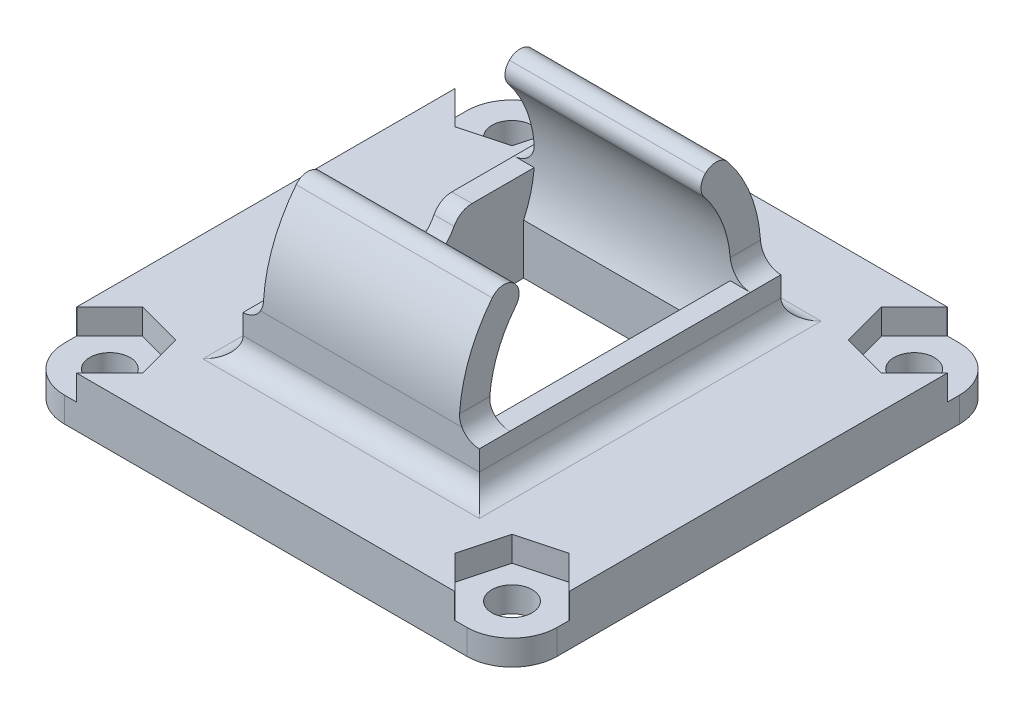
SolidWorks part; units mm, degrees
ref_plane "Front Plane" through (0, 0, 0) normal (0, 0, 1) x (1, 0, 0)
ref_plane "Top Plane" through (0, 0, 0) normal (0, 1, 0) x (1, 0, 0)
ref_plane "Right Plane" through (0, 0, 0) normal (1, 0, 0) x (0, 0, -1)
sketch "Sketch1" plane through (0, 0, 0) normal (0, 1, 0) x (1, 0, 0)
  line L1 (10, 10) -> (-10, 10)
  line L2 (10, 10) -> (10, -10)
  line L3 (10, -10) -> (-10, -10)
  line L4 (-10, 10) -> (-10, -10)
  line L5 (10, 10) -> (-10, -10) construction
  line L6 (10, -10) -> (-10, 10) construction
  circle A0 centre (-10, 10) radius 1
  circle A1 centre (10, 10) radius 1
  circle A2 centre (10, -10) radius 2.25
  circle A3 centre (-10, -10) radius 1
  circle A4 centre (-10, 10) radius 2.25
  circle A5 centre (10, 10) radius 2.25
  circle A6 centre (10, -10) radius 1
  circle A7 centre (-10, -10) radius 2.25
  point P0 (0, 0)
  dimension "D2" = 2
  dimension "D3" = 4.5
  dimension "D1" = 20
extrude "Boss-Extrude1" add sketch "Sketch1" along normal blind 2.5 contours A7 | A3 | A2 | A6 | A5 | A1 | A4 | A0
sketch "Sketch2" plane through (0, 2.5, 0) normal (0, 1, 0) x (1, 0, 0)
  line L0 (-12.25, 10) -> (-12.25, -10)
  line L1 (-10, -12.25) -> (10, -12.25)
  line L2 (12.25, -10) -> (12.25, 10)
  line L3 (-10, 12.25) -> (10, 12.25)
  circle A0 centre (10, 10) radius 2.25 construction
  circle A1 centre (10, -10) radius 2.25 construction
  circle A2 centre (-10, -10) radius 2.25 construction
  circle A3 centre (-10, 10) radius 2.25 construction
  circle A4 centre (10, 10) radius 2.25
  circle A5 centre (10, -10) radius 2.25
  circle A6 centre (-10, -10) radius 2.25
  circle A7 centre (-10, 10) radius 2.25
  circle A8 centre (10, 10) radius 1 construction
  circle A9 centre (10, -10) radius 1 construction
  circle A10 centre (-10, -10) radius 1 construction
  circle A11 centre (-10, 10) radius 1 construction
  circle A12 centre (10, 10) radius 1
  circle A13 centre (10, -10) radius 1
  circle A14 centre (-10, -10) radius 1
  circle A15 centre (-10, 10) radius 1
  circle M5 centre (-10, 10) radius 2.25
  circle M6 centre (-10, 10) radius 1
extrude "Boss-Extrude2" add sketch "Sketch2" along normal blind 2.5 contours A6 L1 A5 L2 A4 L3 L0 M5 | M5 M6 | A4 A12 | A5 A13 | A6 A14 region at (0, 2.5, 0) region at (-11.546, 2.5, -11.546) region at (-10, 2.5, 7.8136) region at (11.546, 2.5, -11.546) region at (8.454, 2.5, 8.454)
sketch "Sketch5" plane through (0, 0, 0) normal (1, 0, 0) x (0, 0, -1)
  line L0 (0, 12.969) -> (0, -5.1317) construction
  line L2 (0, 1.5) -> (-5.3522, 1.5) construction
  line L3 (-10, 2.5) -> (10, 2.5) construction
  line L4 (0, 7.5) -> (-5.3033, 12.8033)
  line L5 (0, 7.5) -> (-7.5, 7.5) construction
  line L6 (0, 7.5) -> (5.3033, 12.8033)
  line L7 (-10, 5) -> (10, 5) construction
  line L8 (-10, 5) -> (10, 5)
  line L9 (-7.5, 7.5) -> (-7.5, 5)
  line L10 (7.5, 7.5) -> (7.5, 5)
  circle A0 centre (0, 7.5) radius 6
  circle A1 centre (0, 7.5) radius 7.5
  dimension "D1" = 12
  dimension "D3" = 1.5
  dimension "D2" = 1
  dimension "D4" = 45
extrude "Boss-Extrude4" add sketch "Sketch5" along normal mid plane 9.75 contours L4 A1 L8 A0 | A1 L9 L8 | A1 L6 A0 L8 | A1 L8 L10 region at (0, 8.7918, 6.2601) region at (0, 8.7918, -6.2601) region at (0, 5.6214, 7.372) region at (0, 5.6214, -7.372)
sketch "Sketch6" plane through (0, 5, 0) normal (0, 1, 0) x (1, 0, 0)
  line L0 (4.875, -7.5) -> (-4.875, -7.5) construction
  line L1 (-4.875, 7.5) -> (-5.875, 7.5)
  line L2 (-4.875, 7.5) -> (-4.875, -7.5)
  line L3 (-4.875, -7.5) -> (-5.875, -7.5)
  line L4 (-5.875, 7.5) -> (-5.875, -7.5)
  line L5 (0, 12.25) -> (0, -12.25) construction
  line L6 (-10, 12.25) -> (10, 12.25) construction
  line L7 (-10, -12.25) -> (10, -12.25) construction
  line L8 (4.875, 7.5) -> (5.875, 7.5)
  line L9 (4.875, 7.5) -> (4.875, -7.5)
  line L10 (4.875, -7.5) -> (5.875, -7.5)
  line L11 (5.875, 7.5) -> (5.875, -7.5)
  dimension "D1" = 1
extrude "Boss-Extrude5" add sketch "Sketch6" along normal blind 2
sketch "Sketch7" plane through (0, 5, 0) normal (0, 1, 0) x (1, 0, 0)
  line L4 (-4.875, -5.4544) -> (4.875, -5.4544)
  line L5 (4.875, -5.4544) -> (4.875, 5.4544)
  line L6 (4.875, 5.4544) -> (-4.875, 5.4544)
  line L7 (-4.875, 5.4544) -> (-4.875, -5.4544)
  line L8 (-4.875, -5.4544) -> (4.875, -5.4544)
  line L9 (4.875, -5.4544) -> (4.875, 5.4544)
  line L10 (4.875, 5.4544) -> (-4.875, 5.4544)
  line L11 (-4.875, 5.4544) -> (-4.875, -5.4544)
  dimension "D1" = 0
extrude "Cut-Extrude1" cut sketch "Sketch7" against normal up to next
sketch "Sketch8" plane through (-5.875, 0, 0) normal (-1, 0, 0) x (0, 0, 1)
  circle A0 centre (0, 7.5) radius 2.25
  dimension "D1" = 4.5
extrude "Cut-Extrude2" cut sketch "Sketch8" against normal up to next
fillet "Fillet1" radius 0.75 4 edges at (0, 12.8033, -5.3033) (0, 11.7426, -4.2426) (0, 12.8033, 5.3033) (0, 11.7426, 4.2426)
fillet "Fillet2" radius 1 10 edges at (0, 5, -7.5) (0, 5, 7.5) (5.875, 5, 0) (-5.875, 5, 0) (-4.875, 7, 6.7396) (-4.875, 7, -6.7396) (4.875, 7, 6.7396) (4.875, 7, -6.7396) (-5.375, 7, 2.1937) (-5.375, 7, -2.1937)
sketch "Sketch9" plane through (0, 0, 0) normal (0, -1, 0) x (1, 0, 0)
  line L1 (-10, 12.25) -> (10, 12.25) construction
  line L2 (12.25, -12.25) -> (-12.25, -12.25)
  line L3 (12.25, -12.25) -> (12.25, 12.25)
  line L4 (12.25, 12.25) -> (-12.25, 12.25)
  line L5 (-12.25, -12.25) -> (-12.25, 12.25)
  line L6 (12.25, -12.25) -> (-12.25, 12.25) construction
  line L7 (12.25, 12.25) -> (-12.25, -12.25) construction
  line L8 (-12.25, -10) -> (-12.25, 10) construction
  point P2 (0, 0)
extrude "Cut-Extrude3" cut sketch "Sketch9" against normal up to surface (2.5 mm away) up to face at (0, 2.5, 0)
sketch "Sketch10" plane through (0, 5, 0) normal (0, 1, 0) x (1, 0, 0)
  line L0 (0, 0) -> (-11.591, 11.591) construction
  line L1 (-10.5977, 7.7693) -> (-8.367, 8.367)
  line L2 (-8.367, 8.367) -> (-7.7693, 10.5977)
  line L3 (-7.7693, 10.5977) -> (-9.4023, 12.2307)
  line L4 (-9.4023, 12.2307) -> (-11.633, 11.633)
  line L5 (-11.633, 11.633) -> (-12.2307, 9.4023)
  line L6 (-12.2307, 9.4023) -> (-10.5977, 7.7693)
  line L7 (0, 12.25) -> (0, -12.25) construction
  line L8 (-12.25, 0) -> (12.25, 0) construction
  line L9 (12.2307, 9.4023) -> (10.5977, 7.7693)
  line L10 (11.633, 11.633) -> (12.2307, 9.4023)
  line L11 (-12.25, 10) -> (-12.25, -10)
  line L12 (-10, -12.25) -> (10, -12.25)
  line L13 (12.25, -10) -> (12.25, 10)
  line L14 (10, 12.25) -> (-10, 12.25)
  line L15 (-12.25, 10) -> (-12.25, -10)
  line L16 (-10, -12.25) -> (10, -12.25)
  line L17 (12.25, -10) -> (12.25, 10)
  line L18 (10, 12.25) -> (-10, 12.25)
  line L19 (9.4023, 12.2307) -> (11.633, 11.633)
  line L20 (7.7693, 10.5977) -> (9.4023, 12.2307)
  line L21 (8.367, 8.367) -> (7.7693, 10.5977)
  line L22 (10.5977, 7.7693) -> (8.367, 8.367)
  line L23 (11.633, -11.633) -> (12.2307, -9.4023)
  line L24 (9.4023, -12.2307) -> (11.633, -11.633)
  line L25 (7.7693, -10.5977) -> (9.4023, -12.2307)
  line L26 (8.367, -8.367) -> (7.7693, -10.5977)
  line L27 (10.5977, -7.7693) -> (8.367, -8.367)
  line L28 (12.2307, -9.4023) -> (10.5977, -7.7693)
  line L29 (-10.5977, -7.7693) -> (-8.367, -8.367)
  line L30 (-12.2307, -9.4023) -> (-10.5977, -7.7693)
  line L31 (-11.633, -11.633) -> (-12.2307, -9.4023)
  line L32 (-9.4023, -12.2307) -> (-11.633, -11.633)
  line L33 (-7.7693, -10.5977) -> (-9.4023, -12.2307)
  line L34 (-8.367, -8.367) -> (-7.7693, -10.5977)
  line L35 (-12.2307, 9.4023) -> (-12.25, 9.4023)
  line L36 (-12.25, 10) -> (-12.25, -10) construction
  line L37 (-9.4023, 12.2307) -> (-9.4023, 12.25)
  line L38 (9.4023, 12.2307) -> (9.4023, 12.25)
  line L39 (12.2307, 9.4023) -> (12.25, 9.4023)
  line L40 (9.4023, -12.2307) -> (9.4023, -12.25)
  line L41 (12.2307, -9.4023) -> (12.25, -9.4023)
  line L42 (-9.4023, -12.2307) -> (-9.4023, -12.25)
  line L43 (-12.2307, -9.4023) -> (-12.25, -9.4023)
  circle A0 centre (-10, 10) radius 2 construction
  arc A1 (-10, 12.25) -> (-12.25, 10) centre (-10, 10) ccw construction
  arc A6 (-12.25, -10) -> (-10, -12.25) centre (-10, -10) ccw
  arc A7 (10, -12.25) -> (12.25, -10) centre (10, -10) ccw
  arc A8 (12.25, 10) -> (10, 12.25) centre (10, 10) ccw
  arc A9 (-10, 12.25) -> (-12.25, 10) centre (-10, 10) ccw
  arc A10 (-12.25, -10) -> (-10, -12.25) centre (-10, -10) ccw
  arc A11 (10, -12.25) -> (12.25, -10) centre (10, -10) ccw
  arc A12 (12.25, 10) -> (10, 12.25) centre (10, 10) ccw
  arc A13 (-10, 12.25) -> (-12.25, 10) centre (-10, 10) ccw
  line M28 (-12.25, 10) -> (-12.25, -10)
  arc M29 (-12.25, -10) -> (-10, -12.25) centre (-10, -10) ccw
  line M30 (-10, -12.25) -> (10, -12.25)
  arc M31 (10, -12.25) -> (12.25, -10) centre (10, -10) ccw
  line M32 (12.25, -10) -> (12.25, 10)
  arc M33 (12.25, 10) -> (10, 12.25) centre (10, 10) ccw
  line M34 (10, 12.25) -> (-10, 12.25)
  arc M35 (-10, 12.25) -> (-12.25, 10) centre (-10, 10) ccw
  circle M36 centre (-10, 10) radius 1
  circle M37 centre (10, 10) radius 1
  circle M38 centre (10, -10) radius 1
  circle M39 centre (-10, -10) radius 1
  dimension "D1" = 4
  dimension "D2" = 0
extrude "Cut-Extrude4" cut sketch "Sketch10" against normal blind 1.25 contours L5 L6 L1 L2 L3 L4 M35 M36 | L22 L9 L10 L19 L20 L21 M33 M37 | L34 L29 L30 L31 L32 L33 M29 M39 | L23 L28 L27 L26 L25 L24 M31 M38 | L31 L43 M28 M29 | L42 L32 M29 M30 | L24 L40 L16 M31 | L41 L23 M31 M32 | L38 L19 M33 M34 | L10 L39 L17 M33 | L35 L5 M35 M28 | L4 L37 L18 M35 region at (-11.3696, 5, -8.6304) region at (-12.0359, 5, -10.5106) region at (-10.5106, 5, -12.0359) region at (-12.0359, 5, 10.5106) region at (-11.3696, 5, 8.6304) region at (10.5106, 5, -12.0359) region at (10.4415, 5, -11.8869) region at (-10.5106, 5, 12.0359) region at (12.0359, 5, -10.5106) region at (10.5106, 5, 12.0359) region at (8.6304, 5, 11.3696) region at (12.0359, 5, 10.5106)
